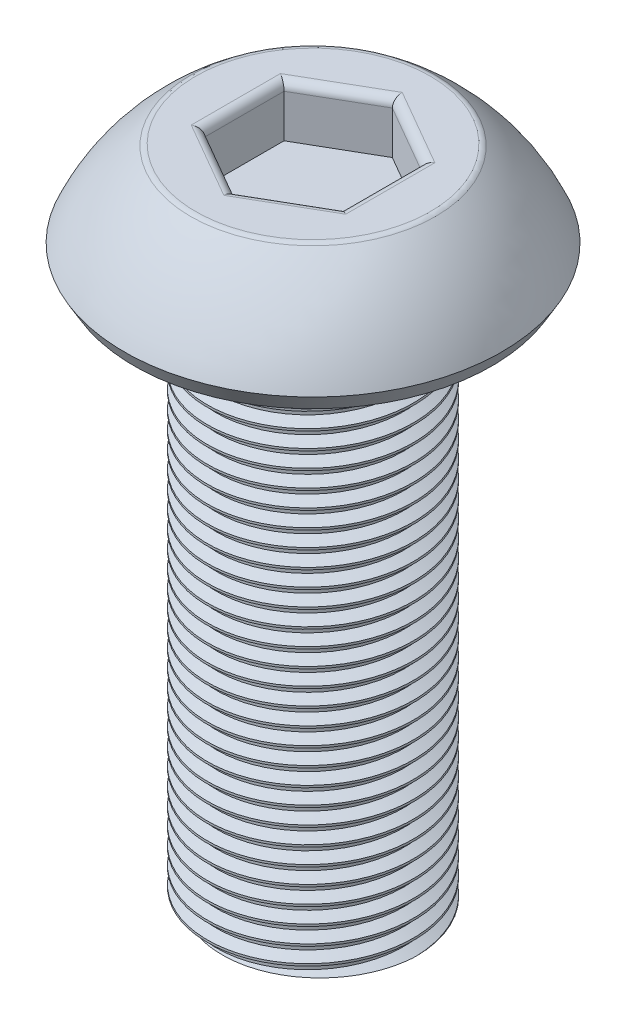
SolidWorks part; units mm, degrees
ref_plane "Front Plane" through (0, 0, 0) normal (0, 0, 1) x (1, 0, 0)
ref_plane "Top Plane" through (0, 0, 0) normal (0, 1, 0) x (1, 0, 0)
ref_plane "Right Plane" through (0, 0, 0) normal (1, 0, 0) x (0, 0, -1)
sketch "Sketch1" plane through (0, 0, 0) normal (1, 0, 0) x (0, 0, -1)
  line L0 (0, 0) -> (0, 1.5) construction
  line L1 (0, 1.5) -> (-1.75, 1.5)
  line L3 (-2.75, 0.25) -> (-2.6057, 0)
  line L4 (-2.6057, 0) -> (-1.5, 0)
  line L5 (-1.5, 0) -> (-1.5, -8)
  line L6 (-1.5, -8) -> (0, -8)
  line L7 (0, -8) -> (0, 1.5)
  line L8 (0, 0) -> (-1.5, 0) construction
  arc A0 (-1.75, 1.5) -> (-2.75, 0.25) centre (0.0077, -0.9312) ccw
  dimension "D5" = 3
  dimension "D1" = 1.5
  dimension "D2" = 2.75
  dimension "D3" = 1.75
  dimension "D4" = 0.25
  dimension "D6" = 60
  dimension "D7" = 1.5
  dimension "D8" = 8
revolve "Revolve1" add sketch "Sketch1" angle 360 about L7
sketch "Sketch2" plane through (0, 1.5, 0) normal (0, 1, 0) x (1, 0, 0)
  line L1 (0, 1.1547) -> (-1, 0.5774)
  line L2 (-1, 0.5774) -> (-1, -0.5774)
  line L3 (-1, -0.5774) -> (0, -1.1547)
  line L4 (0, -1.1547) -> (1, -0.5774)
  line L5 (1, -0.5774) -> (1, 0.5774)
  line L6 (1, 0.5774) -> (0, 1.1547)
  circle A0 centre (0, 0) radius 1 construction
  dimension "D1" = 2
extrude "Cut-Extrude1" cut sketch "Sketch2" against normal blind 0.75
fillet "Fillet1" radius 0.125 7 edges at (0, 1.5, -1.75) (-0.5, 1.5, 0.866) (0.5, 1.5, 0.866) (1, 1.5, 0) (0.5, 1.5, -0.866) (-0.5, 1.5, -0.866) (-1, 1.5, 0)
thread "Thread1" pitch 0.25 method cut profile "Thread Profile1" start angle 0, offset 1, length 8.75, pitch 0.25, diameter 3
ref_plane "Plane1" through (1.5, -9, 0) normal (0, 0, 1) x (1, 0, 0)
sketch "Thread Profile1" plane through (1.5, -9, 0) normal (0, 0, 1) x (1, 0, 0)
  line L0 (0, 0) -> (0, 0.25) construction
  line L11 (0, 0) -> (0, 0.2187)
  line L12 (0, 0.2187) -> (-0.1353, 0.1406)
  line L13 (-0.1353, 0.1406) -> (-0.1353, 0.0781)
  line L15 (-0.1353, 0.0781) -> (0, 0)
  line L17 (-0.1353, 0.1094) -> (0, 0.1094) construction
  point P2 (0, 0)
  dimension "Pitch" = 0.25
  dimension "Profile_Angle" = 60
  dimension "Profile_Land" = 0.0625
  dimension "Profile_Height" = 0.1353
